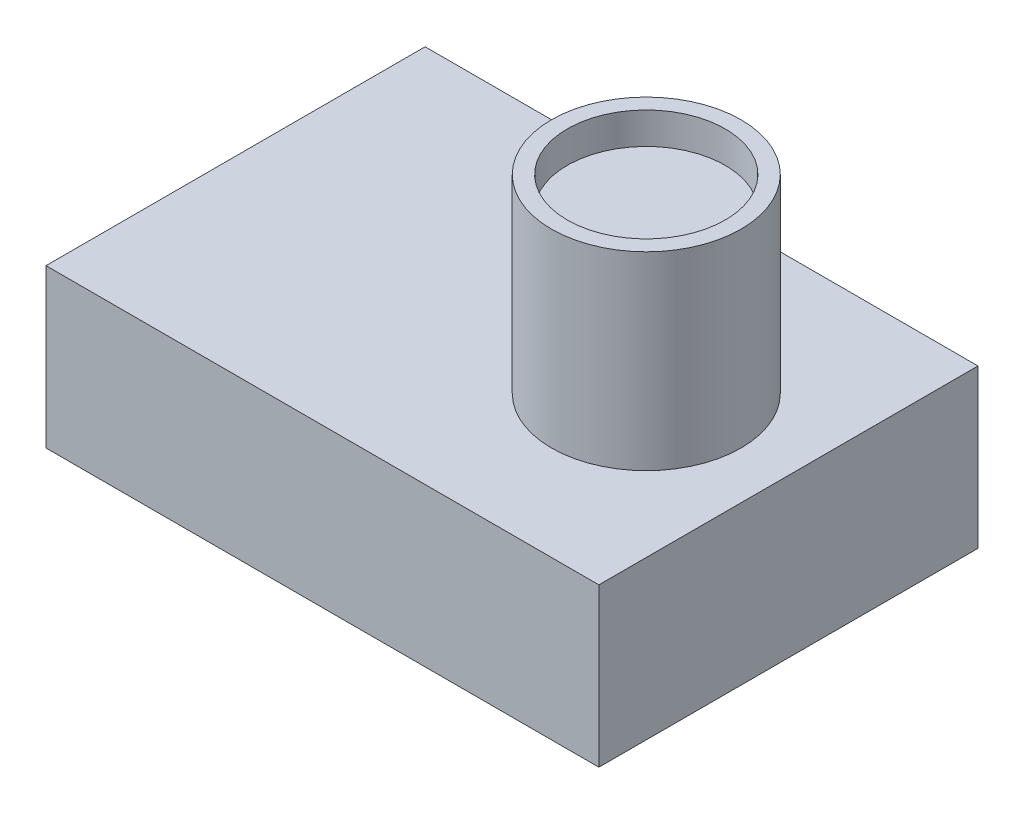
SolidWorks part; units mm, degrees
material "1060 Alloy"
ref_plane "Front Plane" through (0, 0, 0) normal (0, 0, 1) x (1, 0, 0)
ref_plane "Top Plane" through (0, 0, 0) normal (0, 1, 0) x (1, 0, 0)
ref_plane "Right Plane" through (0, 0, 0) normal (1, 0, 0) x (0, 0, -1)
sketch "Sketch2" plane through (0, 0, 0) normal (0, 1, 0) x (1, 0, 0)
  line L1 (-17.5, 12) -> (17.5, 12)
  line L2 (-17.5, 12) -> (-17.5, -12)
  line L3 (-17.5, -12) -> (17.5, -12)
  line L4 (17.5, 12) -> (17.5, -12)
  line L5 (-17.5, 12) -> (17.5, -12) construction
  line L6 (-17.5, -12) -> (17.5, 12) construction
  point P0 (0, 0)
  dimension "D1" = 35
  dimension "D2" = 24
extrude "Boss-Extrude1" add sketch "Sketch2" along normal blind 10
sketch "Sketch3" plane through (0, 10, 0) normal (0, 1, 0) x (1, 0, 0)
  line L0 (17.5, -12) -> (17.5, 12) construction
  circle A0 centre (8.5, 0) radius 6
  point P2 (0, 0)
  dimension "D1" = 12
  dimension "D2" = 9
extrude "Boss-Extrude2" add sketch "Sketch3" along normal blind 12
sketch "Sketch4" plane through (0, 22, 0) normal (0, 1, 0) x (1, 0, 0)
  circle A0 centre (8.5, 0) radius 5
  circle A1 centre (8.5, 0) radius 6 construction
  dimension "D1" = 10
extrude "Cut-Extrude2" cut sketch "Sketch4" against normal blind 2
